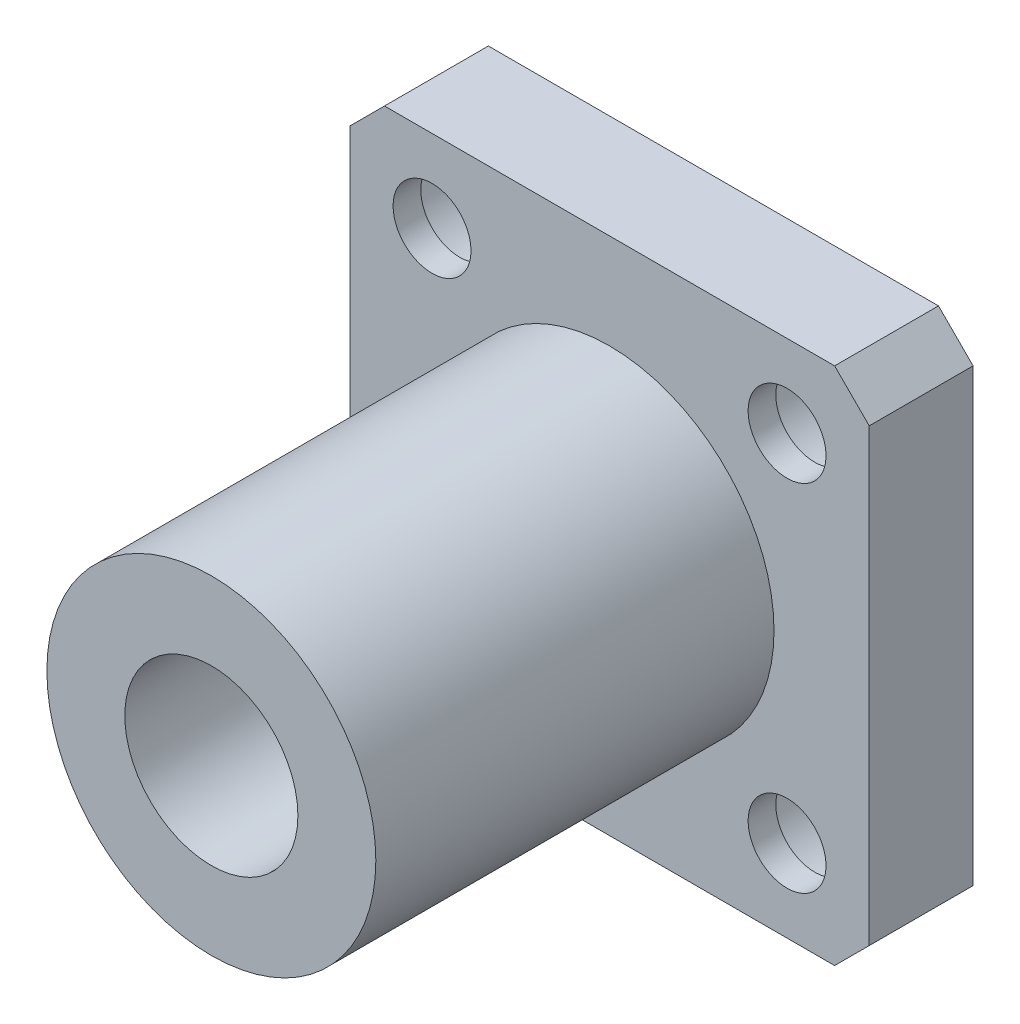
SolidWorks part; units mm, degrees
ref_plane "Płaszczyzna przednia" through (0, 0, 0) normal (0, 0, 1) x (1, 0, 0)
ref_plane "Płaszczyzna górna" through (0, 0, 0) normal (0, 1, 0) x (1, 0, 0)
ref_plane "Płaszczyzna prawa" through (0, 0, 0) normal (1, 0, 0) x (0, 0, -1)
sketch "Sketch1" plane through (0, 0, 0) normal (0, 0, 1) x (1, 0, 0)
  line L1 (0, 0) -> (30, 0)
  line L2 (0, 0) -> (0, 30)
  line L3 (0, 30) -> (30, 30)
  line L4 (30, 0) -> (30, 30)
  dimension "K" = 30
extrude "Boss-Extrude1" add sketch "Sketch1" along normal blind 6
sketch "Sketch2" plane through (0, 0, 6) normal (0, 0, 1) x (1, 0, 0)
  line L0 (0, 15) -> (30, 15) construction
  line L1 (0, 30) -> (0, 0) construction
  line L2 (30, 0) -> (30, 30) construction
  line L3 (15, 0) -> (15, 30) construction
  line L4 (0, 0) -> (30, 0) construction
  line L5 (30, 30) -> (0, 30) construction
  circle A0 centre (15, 15) radius 9.5
  point P15 (15, 15)
  dimension "D" = 19
extrude "Boss-Extrude2" add sketch "Sketch2" along normal blind 23
sketch "Sketch3" plane through (0, 0, 29) normal (0, 0, 1) x (1, 0, 0)
  circle A0 centre (15, 15) radius 5
  dimension "D1" = 10
extrude "Cut-Extrude1" cut sketch "Sketch3" against normal through all
sketch "Sketch4" plane through (0, 0, 0) normal (0, 0, -1) x (-1, 0, 0)
  circle A0 centre (-15, 15) radius 14.5 construction
  dimension "PCD" = 29
hole_wizard "CBORE for M5 Hex Head Bolt1" positions "Sketch8" profile "Sketch6" counterbore size "M5" standard "ANSI Metric" end condition through all
sketch "Sketch8" plane through (0, 0, 0) normal (0, 0, -1) x (-1, 0, 0)
  line L0 (-29.5, 15) -> (-15, 29.5) construction
  line L2 (-22.25, 22.25) -> (-30, 30) construction
  circle A0 centre (-15, 15) radius 14.5 construction
  point P0 (-25.253, 25.253)
  point P22 (-4.747, 25.253)
  point P23 (-4.747, 4.747)
  point P24 (-25.253, 4.747)
  dimension "D1" = 4
sketch "Sketch6" plane through (25.253, 25.253, 0) normal (1, 0, 0) x (0, 1, 0)
  line L0 (0, 0) -> (0, 29)
  line L1 (0, 29) -> (2.25, 29)
  line L3 (2.25, 29) -> (2.25, 4.4)
  line L4 (2.25, 4.4) -> (4, 4.4)
  line L5 (4, 4.4) -> (4, 0)
  line L7 (4, 0) -> (0, 0)
  line L11 (0, -6.35) -> (0, 107.95) construction
  dimension "Thru Hole Dia." = 4.5
  dimension "Thru Hole Depth" = 29
  dimension "C'Bore Dia." = 8
  dimension "C'Bore Depth" = 4.4
chamfer "Chamfer1" distance 2 angle 45 4 edges at (0, 30, 3) (30, 30, 3) (30, 0, 3) (0, 0, 3)
